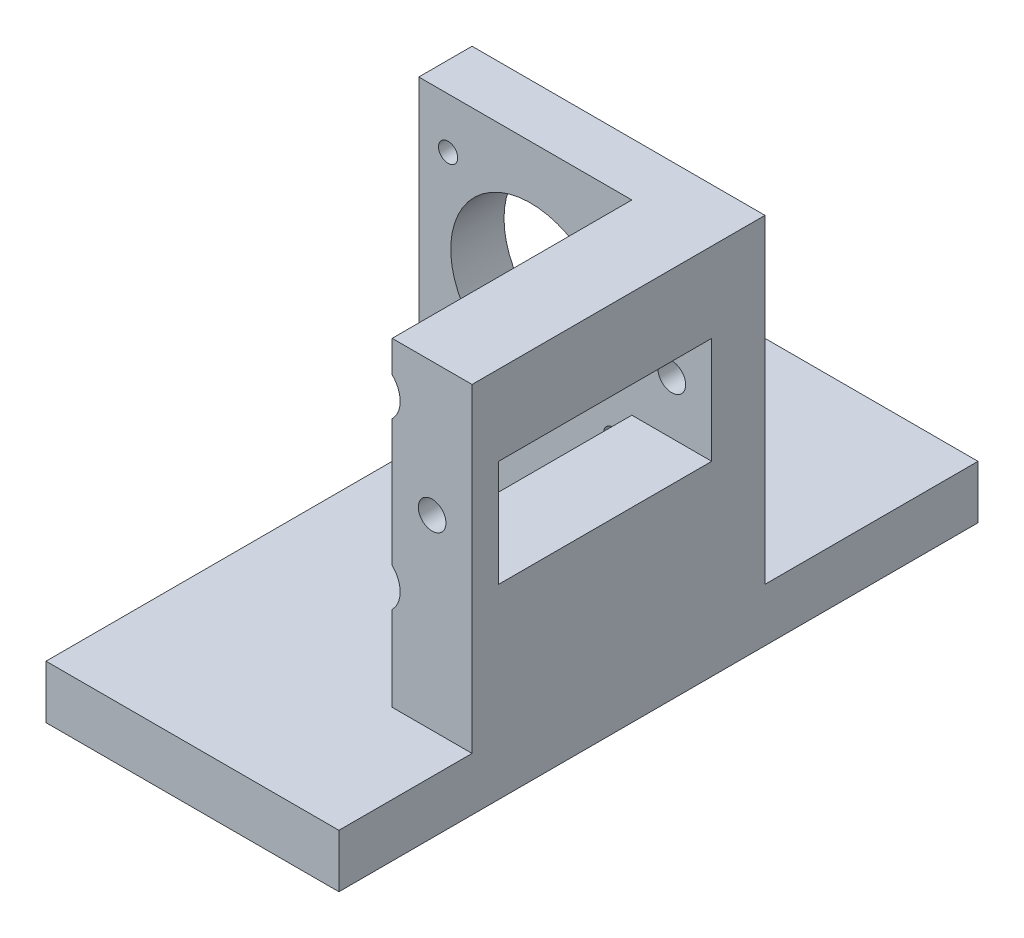
SolidWorks part; units mm, degrees
ref_plane "Front Plane" through (0, 0, 0) normal (0, 0, 1) x (1, 0, 0)
ref_plane "Top Plane" through (0, 0, 0) normal (0, 1, 0) x (1, 0, 0)
ref_plane "Right Plane" through (0, 0, 0) normal (1, 0, 0) x (0, 0, -1)
sketch "Sketch4" plane through (0, 0, 0) normal (0, 1, 0) x (1, 0, 0)
  line L1 (0, 0) -> (40, 0)
  line L2 (0, 0) -> (0, 80)
  line L3 (0, 80) -> (40, 80)
  line L4 (40, 0) -> (40, 80)
  dimension "D1" = 80
  dimension "D2" = 40
extrude "Boss-Extrude4" add sketch "Sketch4" along normal blind 5
sketch "Sketch5" plane through (0, 5, 0) normal (0, 1, 0) x (1, 0, 0)
  line L0 (40, 40) -> (30, 40)
  line L1 (30, 30) -> (30, 50) construction
  line L2 (40, 50) -> (30, 50)
  line L3 (30, 50) -> (30, 55)
  line L4 (0, 80) -> (0, 0)
  line L5 (0, 0) -> (40, 0)
  line L6 (40, 0) -> (40, 80)
  line L7 (40, 80) -> (0, 80)
  line L8 (0, 80) -> (0, 0)
  line L9 (0, 0) -> (40, 0)
  line L10 (40, 0) -> (40, 80)
  line L11 (40, 80) -> (0, 80)
  line L12 (30, 55) -> (40, 55)
  line L13 (40, 55) -> (40, 50)
  line L14 (40, 30) -> (30, 30)
  line L15 (30, 30) -> (30, 25)
  line L16 (30, 25) -> (40, 25)
  line L17 (40, 25) -> (40, 30)
  point P9 (30, 40)
  line M11 (40, 0) -> (40, 80)
  dimension "D2" = 10
  dimension "D3" = 10
  dimension "D4" = 5
  dimension "D5" = 5
  dimension "D1" = 0
extrude "Boss-Extrude6" add sketch "Sketch5" along normal blind 50 contours L12 L3 L2 M11 | L15 L16 L10 L14 region at (35, 5, -52.5) region at (35, 5, -27.5)
sketch "Sketch7" plane through (0, 0, -50) normal (0, 0, 1) x (1, 0, 0)
  line L1 (30, 5) -> (40, 5)
  line L2 (30, 5) -> (30, 30)
  line L3 (30, 30) -> (40, 30)
  line L4 (40, 5) -> (40, 30)
  line L5 (40, 55) -> (40, 5) construction
  line L7 (30, 55) -> (40, 55)
  line L8 (30, 55) -> (30, 50)
  line L9 (30, 50) -> (40, 50)
  line L10 (40, 55) -> (40, 50)
  dimension "D1" = 25
  dimension "D2" = 10
  dimension "D3" = 5
extrude "Boss-Extrude7" add sketch "Sketch7" along normal up to surface (20 mm away) contours L8 L7 L10 L9 | L2 L1 L4 L3 up to face at (35, 30, -30)
sketch "Sketch8" plane through (0, 0, -80) normal (0, 0, -1) x (-1, 0, 0)
  line L4 (-40, 0) -> (0, 0)
  line L5 (0, 0) -> (0, 5)
  line L6 (0, 5) -> (-40, 5)
  line L7 (-40, 5) -> (-40, 0)
  line L8 (-40, 0) -> (0, 0)
  line L9 (0, 0) -> (0, 5)
  line L10 (0, 5) -> (-40, 5)
  line L11 (-40, 5) -> (-40, 0)
  dimension "D1" = 0
extrude "Boss-Extrude8" add sketch "Sketch8" along normal blind 20 contours L8 L9 L10 L11
sketch "Sketch9" plane through (0, 0, 0) normal (-1, 0, 0) x (0, 0, 1)
  line L4 (-100, 0) -> (0, 0)
  line L5 (0, 0) -> (0, 5)
  line L6 (0, 5) -> (-100, 5)
  line L7 (-100, 5) -> (-100, 0)
  line L8 (-100, 0) -> (0, 0)
  line L9 (0, 0) -> (0, 5)
  line L10 (0, 5) -> (-100, 5)
  line L11 (-100, 5) -> (-100, 0)
  dimension "D1" = 0
extrude "Boss-Extrude9" add sketch "Sketch9" along normal blind 10
sketch "Sketch10" plane through (30, 0, 0) normal (-1, 0, 0) x (0, 0, 1)
  line L0 (-25, 5) -> (-55, 5) construction
  line L1 (-55, 55) -> (-50, 55)
  line L2 (-55, 55) -> (-55, 5)
  line L3 (-55, 5) -> (-50, 5)
  line L4 (-50, 55) -> (-50, 5)
  dimension "D1" = 5
extrude "Boss-Extrude10" add sketch "Sketch10" along normal blind 40 contours L2 L1 L4 L3
sketch "Sketch11" plane through (0, 55, 0) normal (0, 1, 0) x (1, 0, 0)
  line L6 (40, 55) -> (-10, 55)
  line L7 (-10, 55) -> (-10, 50)
  line L8 (-10, 50) -> (30, 50)
  line L9 (30, 50) -> (30, 25)
  line L10 (30, 25) -> (40, 25)
  line L11 (40, 25) -> (40, 55)
  line L12 (40, 55) -> (-10, 55)
  line L13 (-10, 55) -> (-10, 50)
  line L14 (-10, 50) -> (30, 50)
  line L15 (30, 50) -> (30, 25)
  line L16 (30, 25) -> (40, 25)
  line L17 (40, 25) -> (40, 55)
  dimension "D1" = 0
extrude "Boss-Extrude11" add sketch "Sketch11" along normal blind 10
sketch "Sketch12" plane through (0, 0, -50) normal (0, 0, 1) x (1, 0, 0)
  line L0 (30, 50) -> (30, 30)
  line L1 (30, 40) -> (26, 40)
  line L2 (0.3934, 50.6066) -> (-3.227, 54.227)
  line L3 (-10, 61) -> (32, 61)
  line L4 (-10, 61) -> (-10, 19)
  line L5 (-10, 19) -> (32, 19)
  line L6 (32, 61) -> (32, 19)
  line L7 (-10, 61) -> (32, 19) construction
  line L8 (30, 30) -> (40, 30)
  line L9 (40, 30) -> (40, 50)
  line L10 (40, 50) -> (30, 50)
  line L11 (30, 50) -> (30, 65)
  line L12 (30, 65) -> (-10, 65)
  line L13 (-10, 65) -> (-10, 5)
  line L14 (-10, 5) -> (30, 5)
  line L15 (30, 5) -> (30, 30)
  line L16 (30, 30) -> (40, 30)
  line L17 (40, 30) -> (40, 50)
  line L18 (40, 50) -> (30, 50)
  line L19 (30, 50) -> (30, 65)
  line L20 (30, 65) -> (-10, 65)
  line L21 (-10, 65) -> (-10, 5)
  line L22 (-10, 5) -> (30, 5)
  line L23 (30, 5) -> (30, 30)
  line L24 (-10, 19) -> (32, 61) construction
  line L25 (-2.6998, 24.5002) -> (-4.4998, 24.5002) construction
  line L26 (24.6998, 24.5002) -> (-2.6998, 24.5002)
  line L27 (26.4998, 26.3002) -> (26.4998, 53.6998)
  line L28 (24.6998, 55.4998) -> (-2.6998, 55.4998)
  line L29 (-4.4998, 26.3002) -> (-4.4998, 53.6998)
  line L30 (26.4998, 24.5002) -> (-4.4998, 55.4998) construction
  line L31 (26.4998, 55.4998) -> (-4.4998, 24.5002) construction
  line L32 (26.4998, 24.5002) -> (24.6998, 24.5002) construction
  line L33 (26.4998, 24.5002) -> (26.4998, 26.3002) construction
  line L34 (26.4998, 53.6998) -> (26.4998, 55.4998) construction
  line L35 (26.4998, 55.4998) -> (24.6998, 55.4998) construction
  line L36 (11, 40) -> (0.3934, 50.6066) construction
  line L37 (26, 40) -> (11, 40) construction
  line L38 (-3.227, 54.227) -> (-4.4998, 55.4998) construction
  line L39 (-4.4998, 53.6998) -> (-4.4998, 55.4998) construction
  line L40 (-2.6998, 55.4998) -> (-4.4998, 55.4998) construction
  line L41 (-4.4998, 24.5002) -> (-4.4998, 26.3002) construction
  circle A0 centre (11, 40) radius 15
  circle A1 centre (-4.4998, 55.4998) radius 1.8
  circle A2 centre (26.4998, 55.4998) radius 1.8
  circle A3 centre (26.4998, 24.5002) radius 1.8
  circle A4 centre (-4.4998, 24.5002) radius 1.8
  dimension "D2" = 19
  dimension "D3" = 30
  dimension "D6" = 3.6
  dimension "D7" = 3.6
  dimension "D1" = 0
  dimension "D4" = 42
  dimension "D5" = 21.92
extrude "Cut-Extrude1" cut sketch "Sketch12" against normal up to surface (5 mm away) contours A0 | A1 | A2 | A4 | A3 region at (11, 40, -50) region at (-4.4998, 55.4998, -50) up to face at (15, 35, -55)
sketch "Sketch13" plane through (0, 0, -50) normal (0, 0, 1) x (1, 0, 0)
  line L0 (40, 40) -> (35, 40) construction
  line L8 (30, 30) -> (40, 30)
  line L9 (40, 30) -> (40, 50)
  line L10 (40, 50) -> (30, 50)
  line L11 (30, 50) -> (30, 65)
  line L12 (30, 65) -> (-10, 65)
  line L13 (-10, 65) -> (-10, 5)
  line L14 (-10, 5) -> (30, 5)
  line L15 (30, 5) -> (30, 30)
  line L16 (30, 30) -> (40, 30)
  line L17 (40, 30) -> (40, 50)
  line L18 (40, 50) -> (30, 50)
  line L19 (30, 50) -> (30, 65)
  line L20 (30, 65) -> (-10, 65)
  line L21 (-10, 65) -> (-10, 5)
  line L22 (-10, 5) -> (30, 5)
  line L23 (30, 5) -> (30, 30)
  circle A0 centre (35, 40) radius 2.25
  dimension "D3" = 4.5
  dimension "D2" = 5
  dimension "D1" = 0
extrude "Cut-Extrude2" cut sketch "Sketch13" against normal through all both and the other way through all contours A0
sketch "Sketch14" plane through (0, 0, -25) normal (0, 0, 1) x (1, 0, 0)
  circle A0 centre (35, 40) radius 2.25 construction
  circle A1 centre (35, 40) radius 2.25
  circle A2 centre (35, 40) radius 4
  dimension "D1" = 8
extrude "Cut-Extrude4" cut sketch "Sketch14" against normal blind 2 contours A1 | A2
sketch "Sketch15" plane through (0, 0, -55) normal (0, 0, -1) x (-1, 0, 0)
  circle A0 centre (-35, 40) radius 2.25 construction
  circle A1 centre (-35, 40) radius 2.25
  circle A2 centre (-35, 40) radius 4
  dimension "D1" = 8
extrude "Cut-Extrude5" cut sketch "Sketch15" against normal blind 2
sketch "Sketch17" plane through (0, 0, -25) normal (0, 0, 1) x (1, 0, 0)
  line L0 (26.4998, 55.4998) -> (26.4998, 24.5002)
  circle A0 centre (26.4998, 55.4998) radius 1.8 construction
  circle A1 centre (26.4998, 55.4998) radius 1.8
  circle A2 centre (26.4998, 55.4998) radius 5
  circle A3 centre (26.4998, 24.5002) radius 5
  line M4 (30, 65) -> (30, 5)
  dimension "D1" = 10
  dimension "D2" = 10
extrude "Cut-Extrude6" cut sketch "Sketch17" against normal up to surface (25 mm away) contours A2 A1 M4 | A3 M4 | A3 M4 | A2 M4 region at (21.9924, 57.3406, -25) region at (26.0733, 24.5002, -25) region at (30.6084, 55.4998, -25) region at (30.6084, 24.5002, -25) up to face at (37.25, 40, -50)
sketch "Sketch19" plane through (0, 0, -55) normal (0, 0, -1) x (-1, 0, 0)
  line L4 (10, 5) -> (10, 65)
  line L5 (10, 65) -> (-40, 65)
  line L6 (-40, 65) -> (-40, 5)
  line L7 (-40, 5) -> (10, 5)
  line L8 (10, 5) -> (10, 65)
  line L9 (10, 65) -> (-40, 65)
  line L10 (-40, 65) -> (-40, 5)
  line L11 (-40, 5) -> (10, 5)
  circle A0 centre (4.4998, 55.4998) radius 1.8 construction
  circle A1 centre (4.4998, 24.5002) radius 1.8 construction
  circle A2 centre (-26.4998, 24.5002) radius 1.8 construction
  circle A3 centre (-11, 40) radius 15 construction
  circle A4 centre (-35, 40) radius 4 construction
  circle A6 centre (-26.4998, 55.4998) radius 1.8 construction
  circle A7 centre (4.4998, 55.4998) radius 1.8
  circle A8 centre (4.4998, 24.5002) radius 1.8
  circle A9 centre (-26.4998, 24.5002) radius 1.8
  circle A10 centre (-11, 40) radius 15
  circle A11 centre (-35, 40) radius 4
  circle A13 centre (-26.4998, 55.4998) radius 1.8
  dimension "D1" = 0
extrude "Boss-Extrude13" add sketch "Sketch19" along normal blind 5
sketch "Sketch20" plane through (0, 0, -53) normal (0, 0, -1) x (-1, 0, 0)
  circle A0 centre (-35, 40) radius 2.25 construction
  circle A1 centre (-35, 40) radius 4
  circle A2 centre (-35, 40) radius 4
  circle A3 centre (-35, 40) radius 2.25
  dimension "D1" = 0
extrude "Boss-Extrude14" add sketch "Sketch20" along normal blind 5
sketch "Sketch21" plane through (40, 0, 0) normal (1, 0, 0) x (0, 0, -1)
  line L0 (50, 50) -> (50, 30) construction
  line L1 (30, 50) -> (30, 30) construction
  line L2 (30, 50) -> (50, 50) construction
  line L3 (30, 30) -> (50, 30) construction
  line L4 (50, 50) -> (50, 30)
  line L5 (30, 50) -> (30, 30)
  line L6 (30, 50) -> (50, 50)
  line L7 (30, 30) -> (50, 30)
  line L8 (100, 5) -> (60, 5)
  line L9 (60, 5) -> (60, 65)
  line L10 (60, 65) -> (25, 65)
  line L11 (25, 65) -> (25, 5)
  line L12 (25, 5) -> (0, 5)
  line L13 (0, 5) -> (0, 0)
  line L14 (0, 0) -> (100, 0)
  line L15 (100, 0) -> (100, 5)
  line L16 (100, 5) -> (60, 5)
  line L17 (60, 5) -> (60, 65)
  line L18 (60, 65) -> (25, 65)
  line L19 (25, 65) -> (25, 5)
  line L20 (25, 5) -> (0, 5)
  line L21 (0, 5) -> (0, 0)
  line L22 (0, 0) -> (100, 0)
  line L23 (100, 0) -> (100, 5)
  dimension "D1" = 0
extrude "Boss-Extrude15" add sketch "Sketch21" along normal blind 5
sketch "Sketch22" plane through (0, 0, -60) normal (0, 0, -1) x (-1, 0, 0)
  circle A0 centre (-35, 40) radius 4 construction
  circle A1 centre (-35, 40) radius 4
extrude "Boss-Extrude16" add sketch "Sketch22" against normal up to surface (10 mm away) up to face at (26.0833, 38.3333, -50)
sketch "Sketch23" plane through (0, 0, -25) normal (0, 0, 1) x (1, 0, 0)
  circle A0 centre (35, 40) radius 4 construction
  circle A1 centre (35, 40) radius 4
extrude "Boss-Extrude17" add sketch "Sketch23" against normal up to surface (5 mm away) up to face at (37.25, 40, -30)
sketch "Sketch24" plane through (0, 0, -30) normal (0, 0, -1) x (-1, 0, 0)
  line L0 (-30, 30) -> (-45, 50) construction
  line L1 (-30, 50) -> (-45, 30) construction
  line L4 (-30, 50) -> (-45, 50)
  line L5 (-45, 50) -> (-45, 30)
  line L6 (-45, 30) -> (-30, 30)
  line L7 (-30, 30) -> (-30, 50)
  line L8 (-30, 50) -> (-45, 50)
  line L9 (-45, 50) -> (-45, 30)
  line L10 (-45, 30) -> (-30, 30)
  line L11 (-30, 30) -> (-30, 50)
  circle A0 centre (-37.5, 40) radius 2.6
  dimension "D2" = 5.2
  dimension "D1" = 0
extrude "Cut-Extrude7" cut sketch "Sketch24" against normal through all both and the other way through all contours A0
sketch "Sketch25" plane through (0, 0, 0) normal (0, -1, 0) x (1, 0, 0)
  line L4 (45, 0) -> (-10, 0)
  line L5 (-10, 0) -> (-10, -100)
  line L6 (-10, -100) -> (45, -100)
  line L7 (45, -100) -> (45, 0)
  line L8 (45, 0) -> (-10, 0)
  line L9 (-10, 0) -> (-10, -100)
  line L10 (-10, -100) -> (45, -100)
  line L11 (45, -100) -> (45, 0)
  dimension "D1" = 0
extrude "Boss-Extrude18" add sketch "Sketch25" along normal blind 5
sketch "Sketch26" plane through (0, 0, 0) normal (0, 0, 1) x (1, 0, 0)
  line L4 (-10, 5) -> (-10, -5)
  line L5 (-10, -5) -> (45, -5)
  line L6 (45, -5) -> (45, 5)
  line L7 (45, 5) -> (-10, 5)
  line L8 (-10, 5) -> (-10, -5)
  line L9 (-10, -5) -> (45, -5)
  line L10 (45, -5) -> (45, 5)
  line L11 (45, 5) -> (-10, 5)
  dimension "D1" = 0
extrude "Boss-Extrude19" add sketch "Sketch26" along normal blind 20
sketch "Sketch27" plane through (30, 0, 0) normal (-1, 0, 0) x (0, 0, 1)
  line L1 (-30, 50) -> (-25, 50)
  line L2 (-30, 50) -> (-30, 30)
  line L3 (-30, 30) -> (-25, 30)
  line L4 (-25, 50) -> (-25, 30)
  line L5 (-25, 51.9293) -> (-25, 28.0707) construction
  dimension "D1" = 5
  dimension "D2" = 20
extrude "Cut-Extrude8" cut sketch "Sketch27" against normal blind 15
sketch "Sketch28" plane through (0, 0, -25) normal (0, 0, 1) x (1, 0, 0)
  line L5 (45, 5) -> (45, 30)
  line L6 (45, 30) -> (30, 30)
  line L7 (30, 30) -> (30, 28.0707)
  line L8 (30, 20.9297) -> (30, 5)
  line L9 (30, 5) -> (45, 5)
  line L10 (45, 5) -> (45, 30)
  line L11 (45, 30) -> (30, 30)
  line L12 (30, 30) -> (30, 28.0707)
  line L13 (30, 20.9297) -> (30, 5)
  line L14 (30, 5) -> (45, 5)
  line L15 (30, 51.9293) -> (30, 50)
  line L16 (30, 50) -> (45, 50)
  line L17 (45, 50) -> (45, 65)
  line L18 (45, 65) -> (30, 65)
  line L19 (30, 65) -> (30, 59.0703)
  line L20 (30, 51.9293) -> (30, 50)
  line L21 (30, 50) -> (45, 50)
  line L22 (45, 50) -> (45, 65)
  line L23 (45, 65) -> (30, 65)
  line L24 (30, 65) -> (30, 59.0703)
  arc A1 (30, 20.9297) -> (30, 28.0707) centre (26.4998, 24.5002) ccw
  arc A2 (30, 20.9297) -> (30, 28.0707) centre (26.4998, 24.5002) ccw
  arc A3 (30, 51.9293) -> (30, 59.0703) centre (26.4998, 55.4998) ccw
  arc A4 (30, 51.9293) -> (30, 59.0703) centre (26.4998, 55.4998) ccw
  dimension "D1" = 0
  dimension "D2" = 0
extrude "Boss-Extrude20" add sketch "Sketch28" along normal blind 20
sketch "Sketch29" plane through (0, 30, 0) normal (0, 1, 0) x (1, 0, 0)
  line L7 (30, 5) -> (45, 5)
  line L8 (30, 5) -> (30, 10)
  line L9 (30, 10) -> (45, 10)
  line L10 (45, 5) -> (45, 10)
  line L11 (45, 5) -> (45, 50) construction
  dimension "D1" = 5
  dimension "D2" = 15
extrude "Boss-Extrude21" add sketch "Sketch29" along normal blind 20
sketch "Sketch30" plane through (0, 0, -60) normal (0, 0, -1) x (-1, 0, 0)
  circle A0 centre (-37.5, 40) radius 2.6 construction
  circle A1 centre (-37.5, 40) radius 2.6
extrude "Cut-Extrude9" cut sketch "Sketch30" against normal blind 60
